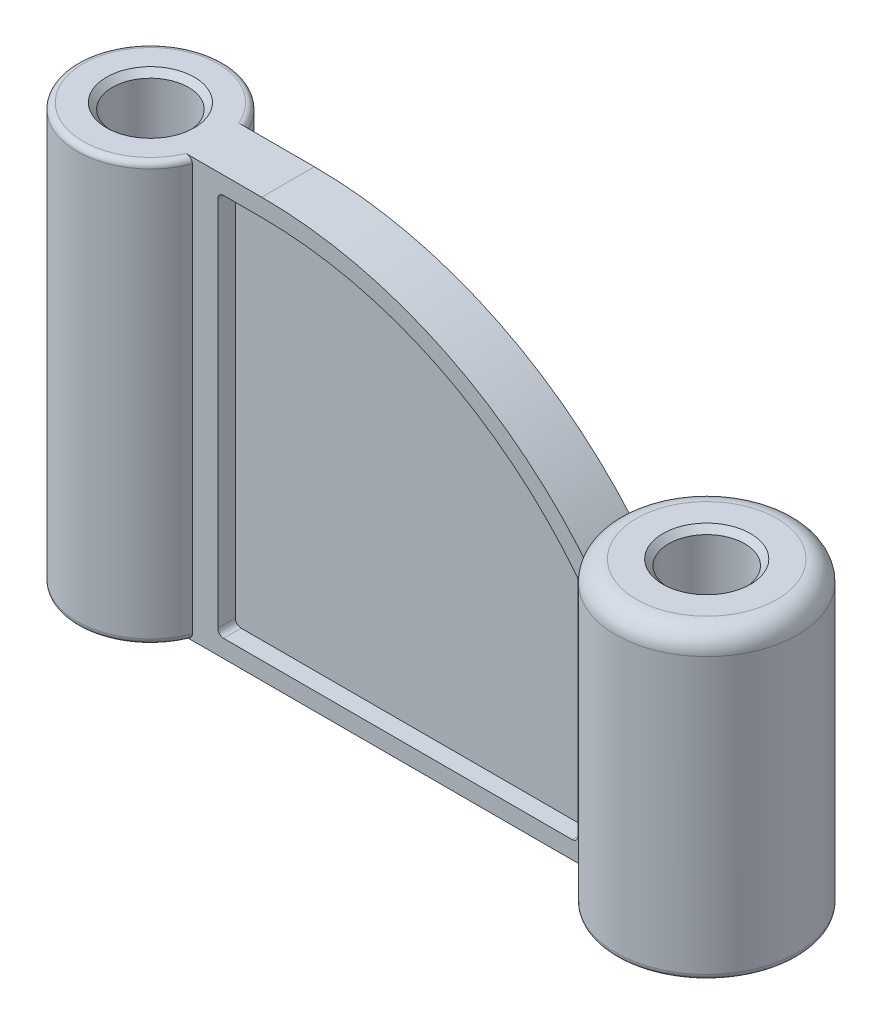
SolidWorks part; units mm, degrees
material "1060 Alloy"
ref_plane "Front Plane" through (0, 0, 0) normal (0, 0, 1) x (1, 0, 0)
ref_plane "Top Plane" through (0, 0, 0) normal (0, 1, 0) x (1, 0, 0)
ref_plane "Right Plane" through (0, 0, 0) normal (1, 0, 0) x (0, 0, -1)
sketch "Sketch1" plane through (0, 0, 0) normal (0, 0, 1) x (1, 0, 0)
  line L1 (143, 0) -> (143, 108.5119) construction
  line L7 (156, 103) -> (174, 103)
  line L8 (156, 103) -> (156, 0)
  line L9 (156, 0) -> (174, 0)
  line L10 (174, 103) -> (174, 0)
  dimension "D4" = 26
  dimension "D5" = 62
  dimension "D6" = 103
  dimension "D7" = 143
revolve "Revolve2" add sketch "Sketch1" angle 360 about L1
sketch "Sketch3" plane through (0, 0, 0) normal (0, 0, 1) x (1, 0, 0)
  line L0 (-47, 0) -> (-47, 103.5252) construction
  line L1 (143, 0) -> (143, 108.5119) construction
  line L2 (-60, 143) -> (-72, 143)
  line L3 (-60, 143) -> (-60, 0)
  line L4 (-60, 0) -> (-72, 0)
  line L5 (-72, 143) -> (-72, 0)
  dimension "D1" = 26
  dimension "D2" = 50
  dimension "D3" = 190
  dimension "D4" = 143
revolve "Revolve3" add sketch "Sketch3" angle 360 about L0
chamfer "Chamfer1" distance 2 angle 45 2 edges at (-47, 0, -13) (-47, 143, -13)
chamfer "Chamfer2" distance 2 angle 45 2 edges at (143, 103, -13) (143, 0, -13)
fillet "Fillet1" radius 2 2 edges at (-47, 143, -25) (-47, 0, -25)
fillet "Fillet2" radius 2 1 edges at (143, 0, -31)
fillet "Fillet3" radius 7 1 edges at (143, 103, -31)
sketch "Sketch4" plane through (0, 0, 0) normal (0, 0, 1) x (1, 0, 0)
  line L5 (0, 0) -> (-27.1933, 0)
  line L6 (-27.1933, 0) -> (-27.1933, 143)
  line L7 (-27.1933, 143) -> (0, 143)
  line L8 (121.3197, 75.7003) -> (121.3197, 0)
  line L9 (121.3197, 0) -> (0, 0)
  arc A1 (0, 143) -> (121.3197, 75.7003) centre (0, 0) cw
  point P7 (0, 0)
  dimension "D1" = 143
extrude "Boss-Extrude1" add sketch "Sketch4" along normal blind 9 and the other way blind 9
sketch "Sketch6" plane through (0, 0, 9) normal (0, 0, 1) x (1, 0, 0)
  line L8 (0, 137) -> (-13, 137)
  line L9 (-15, 135) -> (-15, 8)
  line L10 (-13, 6) -> (106, 6)
  line L11 (108, 8) -> (108, 83.6002)
  line L12 (-25.834, 0) -> (115.4319, 0) construction
  line L13 (-47, 0) -> (-47, 103.5252) construction
  line L14 (143, 0) -> (143, 108.5119) construction
  line L15 (0, 143) -> (-25.834, 143) construction
  arc A2 (107.5704, 84.8388) -> (0, 137) centre (0, 0) ccw
  arc A3 (113.3352, 87.2017) -> (0, 143) centre (0, 0) ccw construction
  arc A4 (106, 6) -> (108, 8) centre (106, 8) ccw
  arc A5 (108, 83.6002) -> (107.5704, 84.8388) centre (106, 83.6002) ccw
  arc A6 (-15, 8) -> (-13, 6) centre (-13, 8) ccw
  arc A7 (-13, 137) -> (-15, 135) centre (-13, 135) ccw
  point P4 (38.9388, 57.465)
  point P5 (0, 0)
  point P6 (95.6172, 38.6628)
  point P7 (5.7758, 128.6188)
  point P8 (0, 0)
  point P11 (0, 0)
  point P13 (0, 127.3586)
  dimension "D1" = 6
  dimension "D6" = 2
  dimension "D2" = 6
  dimension "D3" = 32
  dimension "D4" = 35
  dimension "D5" = 6
extrude "Cut-Extrude1" cut sketch "Sketch6" against normal blind 6
mirror "Mirror1" about plane through (0, 0, 0) normal (0, 0, 1) of "Cut-Extrude1"
sketch "Sketch7" plane through (0, 0, 0) normal (0, 0, 1) x (1, 0, 0)
  line L0 (-72, 143) -> (-72, 0) construction
  line L1 (-72, 115) -> (-21, 115)
  line L2 (-72, 115) -> (-72, 50)
  line L3 (-72, 50) -> (-21, 50)
  line L4 (-21, 115) -> (-21, 50)
  line L6 (-15, 135) -> (-15, 8) construction
  dimension "D1" = 65
  dimension "D2" = 50
  dimension "D3" = 6
equation "\"A\" = 143"
equation "\"D\"= 26"
equation "\"B\" = 62"
equation "\"Y\" = 1.5 * \"B\" + 10"
equation "\"D4@Sketch1\"=\"D\""
equation "\"D5@Sketch1\"=\"B\""
equation "\"D6@Sketch1\"=\"Y\""
equation "\"D7@Sketch1\"=\"A\""
equation "\"C\" = 190"
equation "\"D1@Sketch3\"=\"D\""
equation "\"D3@Sketch3\"=\"C\""
equation "\"D4@Sketch3\"=\"A\""
equation "\"D1@Sketch4\"=\"A\""
